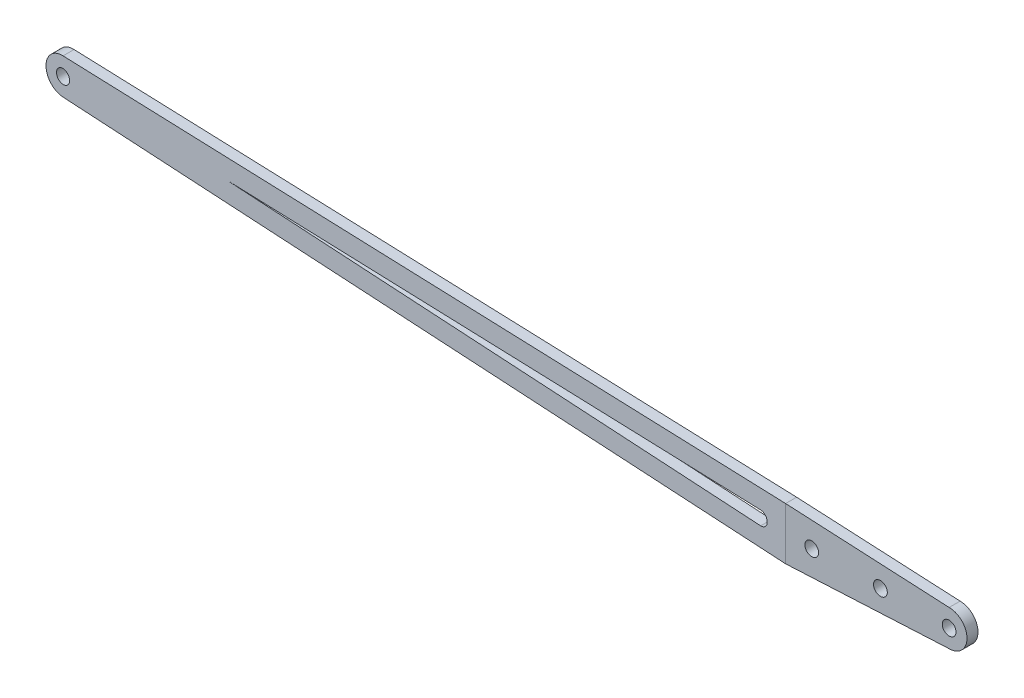
SolidWorks part; units mm, degrees
ref_plane "Front Plane" through (0, 0, 0) normal (0, 0, 1) x (1, 0, 0)
ref_plane "Top Plane" through (0, 0, 0) normal (0, 1, 0) x (1, 0, 0)
ref_plane "Right Plane" through (0, 0, 0) normal (1, 0, 0) x (0, 0, -1)
sketch "Sketch1" plane through (0, 0, 0) normal (0, 1, 0) x (1, 0, 0)
  line L0 (0, 0) -> (-66, 0)
  line L1 (-66, 0) -> (-66, 4)
  line L2 (-66, 4) -> (0, 4)
  line L3 (0, 4) -> (0, 0)
  line L4 (0, 0) -> (-348, 0) construction
  line L5 (-348, 0) -> (-348, 45.819) construction
  line L6 (-348, 45.819) -> (0, 45.819) construction
  line L7 (0, 45.819) -> (0, 0) construction
  line L8 (-348, 0) -> (-348, 12.909)
  line L9 (-66, 0) -> (-348, 12.909)
  line L10 (-348, 12.909) -> (-348, 16.909)
  line L11 (-66, 4) -> (-348, 16.909)
  dimension "D1" = 4
  dimension "D2" = 66
  dimension "D3" = 348
  dimension "D4" = 45.819
  dimension "D5" = 12.909
  dimension "D6" = 4
extrude "Boss-Extrude1" add sketch "Sketch1" along normal blind 19 contours L3 L2 L1 L0 | L1 L11 L10 L9 region at (-33, 0, -2) region at (-207, 0, -8.4545)
sketch "Sketch2" plane through (0, 0, 0) normal (0, 0, 1) x (1, 0, 0)
  line L0 (0, 9.5) -> (-348, 9.5) construction
  line L1 (0, 19) -> (0, 0) construction
  line L2 (-348, 19) -> (-348, 0) construction
  line L3 (0, 9.5) -> (-4, 9.5)
  line L4 (-4, 9.5) -> (-9, 9.5)
  line L5 (-6.5, 3) -> (-6.5, 16)
  line L6 (-9, 9.5) -> (-29, 9.5)
  line L7 (-29, 9.5) -> (-34, 9.5)
  line L8 (-34, 9.5) -> (-54, 9.5)
  line L9 (-54, 9.5) -> (-59, 9.5)
  line L10 (-59, 9.5) -> (-66, 9.5)
  line L11 (-66, 19) -> (-66, 0) construction
  line L12 (-6.5, 16) -> (-66, 19)
  line L13 (-6.5, 3) -> (-66, 0)
  line L14 (-348, 9.5) -> (-344, 9.5)
  line L15 (-344, 9.5) -> (-339, 9.5)
  line L16 (-341.5, 16) -> (-341.5, 3)
  line L17 (-341.5, 16) -> (-66, 19)
  line L18 (-66, 0) -> (-341.5, 3)
  line L19 (-66, 9.5) -> (-73, 9.5)
  line L20 (-73, 9.5) -> (-78, 9.5)
  line L21 (-75.5, 7) -> (-75.5, 12)
  line L22 (-339, 9.5) -> (-279, 9.5)
  line L23 (-279, 9.5) -> (-75.5, 12)
  line L24 (-75.5, 7) -> (-279, 9.5)
  line L25 (-66, 19) -> (0, 19)
  line L26 (0, 19) -> (0, 0)
  line L27 (0, 0) -> (-66, 0)
  line L28 (-66, 0) -> (-348, 0)
  line L29 (-348, 0) -> (-348, 19)
  line L30 (-348, 19) -> (-66, 19)
  circle A0 centre (-6.5, 9.5) radius 2.5
  circle A1 centre (-6.5, 9.5) radius 6.5
  circle A2 centre (-31.5, 9.5) radius 2.5
  circle A3 centre (-56.5, 9.5) radius 2.5
  circle A4 centre (-341.5, 9.5) radius 2.5
  circle A5 centre (-341.5, 9.5) radius 6.5
  circle A6 centre (-75.5, 9.5) radius 2.5
  circle A7 centre (-75.5, 9.5) radius 2.5
  line M12 (-66, 0) -> (0, 0)
  line M13 (0, 0) -> (0, 19)
  line M14 (0, 19) -> (-66, 19)
  dimension "D1" = 4
  dimension "D2" = 5
  dimension "D3" = 6.5
  dimension "D4" = 20
  dimension "D5" = 5
  dimension "D6" = 20
  dimension "D7" = 5
  dimension "D8" = 7
  dimension "D9" = 4
  dimension "D10" = 5
  dimension "D11" = 7
  dimension "D12" = 5
  dimension "D13" = 60
extrude "Cut-Extrude5" cut sketch "Sketch2" against normal blind 40 contours A1 L12 M13 M14 | A1 L13 M12 M13 | L4 A0 L5 | L5 A0 L4 | L4 A0 L5 | L5 A0 L4 | L7 A2 | L7 A2 | L9 A3 | L9 A3 | L20 A6 L21 | L21 A6 L20 | L20 A6 L24 L21 | L23 A6 L20 L21 | L0 A6 L23 | A6 L0 L24 | L15 A4 L16 | L16 A4 L15 | L15 A4 L16 | L16 A4 L15 | A5 L29 L28 L18 | A5 L17 L30 L29 region at (-20.598, 17.6516, 0) region at (-20.598, 1.3484, 0) region at (-5.439, 8.439, 0) region at (-5.439, 10.561, 0) region at (-76.561, 10.561, 0) region at (-144.6472, 8.6711, 0) region at (-7.561, 8.439, 0) region at (-7.561, 10.561, 0) region at (-255.8515, 17.9071, 0) region at (-255.8515, 1.0929, 0) region at (-31.5, 8.439, 0) region at (-31.5, 10.561, 0) region at (-340.439, 10.561, 0) region at (-342.561, 10.561, 0) region at (-342.561, 8.439, 0) region at (-340.439, 8.439, 0) region at (-74.439, 10.561, 0) region at (-144.6472, 10.3289, 0) region at (-56.5, 8.439, 0) region at (-56.5, 10.561, 0) region at (-76.561, 8.439, 0) region at (-74.439, 8.439, 0)
ref_plane "Plane3" through (-0.0467, 0, 1.0191) normal (-0.0457, 0, 0.999) x (0.999, 0, 0.0457)
ref_plane "Plane4" through (0, 0, -2) normal (0, 0, 1) x (1, 0, 0)
